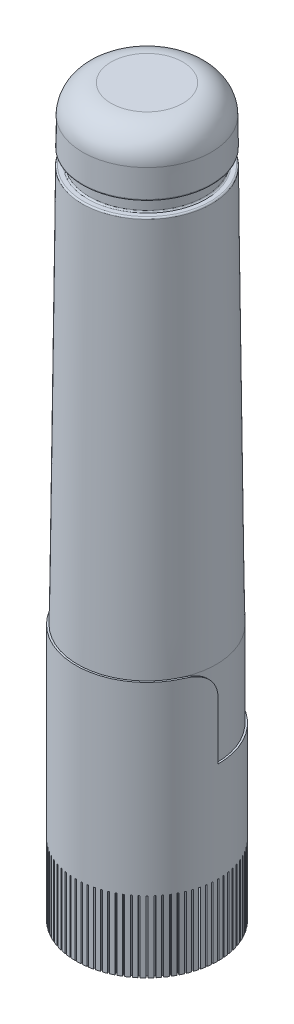
SolidWorks part; units mm, degrees
ref_plane "Front Plane" through (0, 0, 0) normal (0, 0, 1) x (1, 0, 0)
ref_plane "Top Plane" through (0, 0, 0) normal (0, 1, 0) x (1, 0, 0)
ref_plane "Right Plane" through (0, 0, 0) normal (1, 0, 0) x (0, 0, -1)
sketch "Sketch1" plane through (0, 0, 0) normal (0, 1, 0) x (1, 0, 0)
  circle A0 centre (0, 0) radius 5
  dimension "D1" = 10
extrude "Boss-Extrude1" add sketch "Sketch1" along normal blind 18
sketch "Sketch2" plane through (0, 0, 0) normal (0, -1, 0) x (-1, 0, 0)
  line L0 (-0.3559, -5.16) -> (-0.4556, -5.1521)
  line L1 (0.05, -5.172) -> (-0.05, -5.172)
  line L2 (0.05, -5.172) -> (0.05, -4.828)
  line L3 (0.05, -4.828) -> (-0.05, -4.828)
  line L4 (-0.05, -5.172) -> (-0.05, -4.828)
  line L5 (0.05, -5.172) -> (-0.05, -4.828) construction
  line L6 (0.05, -4.828) -> (-0.05, -5.172) construction
  line L7 (-0.3559, -5.16) -> (-0.329, -4.817)
  line L8 (-0.4556, -5.1521) -> (-0.4286, -4.8092)
  line L9 (-0.329, -4.817) -> (-0.4286, -4.8092)
  line L10 (-0.7597, -5.1162) -> (-0.8585, -5.1005)
  line L11 (-0.7597, -5.1162) -> (-0.7059, -4.7764)
  line L12 (-0.8585, -5.1005) -> (-0.8046, -4.7607)
  line L13 (-0.7059, -4.7764) -> (-0.8046, -4.7607)
  line L14 (-1.1588, -5.0408) -> (-1.256, -5.0174)
  line L15 (-1.1588, -5.0408) -> (-1.0785, -4.7063)
  line L16 (-1.256, -5.0174) -> (-1.1757, -4.6829)
  line L17 (-1.0785, -4.7063) -> (-1.1757, -4.6829)
  line L18 (-1.5507, -4.9343) -> (-1.6458, -4.9034)
  line L19 (-1.5507, -4.9343) -> (-1.4444, -4.6071)
  line L20 (-1.6458, -4.9034) -> (-1.5395, -4.5762)
  line L21 (-1.4444, -4.6071) -> (-1.5395, -4.5762)
  line L22 (-1.933, -4.7974) -> (-2.0254, -4.7592)
  line L23 (-1.933, -4.7974) -> (-1.8014, -4.4796)
  line L24 (-2.0254, -4.7592) -> (-1.8938, -4.4413)
  line L25 (-1.8014, -4.4796) -> (-1.8938, -4.4413)
  line L26 (-2.3035, -4.631) -> (-2.3926, -4.5856)
  line L27 (-2.3035, -4.631) -> (-2.1473, -4.3245)
  line L28 (-2.3926, -4.5856) -> (-2.2364, -4.2791)
  line L29 (-2.1473, -4.3245) -> (-2.2364, -4.2791)
  line L30 (-2.6597, -4.436) -> (-2.745, -4.3837)
  line L31 (-2.6597, -4.436) -> (-2.48, -4.1427)
  line L32 (-2.745, -4.3837) -> (-2.5652, -4.0904)
  line L33 (-2.48, -4.1427) -> (-2.5652, -4.0904)
  line L34 (-2.9996, -4.2136) -> (-3.0805, -4.1549)
  line L35 (-2.9996, -4.2136) -> (-2.7974, -3.9353)
  line L36 (-3.0805, -4.1549) -> (-2.8783, -3.8765)
  line L37 (-2.7974, -3.9353) -> (-2.8783, -3.8765)
  line L38 (-3.3209, -3.9653) -> (-3.397, -3.9004)
  line L39 (-3.3209, -3.9653) -> (-3.0975, -3.7037)
  line L40 (-3.397, -3.9004) -> (-3.1735, -3.6388)
  line L41 (-3.0975, -3.7037) -> (-3.1735, -3.6388)
  line L42 (-3.6218, -3.6925) -> (-3.6925, -3.6218)
  line L43 (-3.6218, -3.6925) -> (-3.3785, -3.4493)
  line L44 (-3.6925, -3.6218) -> (-3.4493, -3.3785)
  line L45 (-3.3785, -3.4493) -> (-3.4493, -3.3785)
  line L46 (-3.9004, -3.397) -> (-3.9653, -3.3209)
  line L47 (-3.9004, -3.397) -> (-3.6388, -3.1735)
  line L48 (-3.9653, -3.3209) -> (-3.7037, -3.0975)
  line L49 (-3.6388, -3.1735) -> (-3.7037, -3.0975)
  line L50 (-4.1549, -3.0805) -> (-4.2136, -2.9996)
  line L51 (-4.1549, -3.0805) -> (-3.8765, -2.8783)
  line L52 (-4.2136, -2.9996) -> (-3.9353, -2.7974)
  line L53 (-3.8765, -2.8783) -> (-3.9353, -2.7974)
  line L54 (-4.3837, -2.745) -> (-4.436, -2.6597)
  line L55 (-4.3837, -2.745) -> (-4.0904, -2.5652)
  line L56 (-4.436, -2.6597) -> (-4.1427, -2.48)
  line L57 (-4.0904, -2.5652) -> (-4.1427, -2.48)
  line L58 (-4.5856, -2.3926) -> (-4.631, -2.3035)
  line L59 (-4.5856, -2.3926) -> (-4.2791, -2.2364)
  line L60 (-4.631, -2.3035) -> (-4.3245, -2.1473)
  line L61 (-4.2791, -2.2364) -> (-4.3245, -2.1473)
  line L62 (-4.7592, -2.0254) -> (-4.7974, -1.933)
  line L63 (-4.7592, -2.0254) -> (-4.4413, -1.8938)
  line L64 (-4.7974, -1.933) -> (-4.4796, -1.8014)
  line L65 (-4.4413, -1.8938) -> (-4.4796, -1.8014)
  line L66 (-4.9034, -1.6458) -> (-4.9343, -1.5507)
  line L67 (-4.9034, -1.6458) -> (-4.5762, -1.5395)
  line L68 (-4.9343, -1.5507) -> (-4.6071, -1.4444)
  line L69 (-4.5762, -1.5395) -> (-4.6071, -1.4444)
  line L70 (-5.0174, -1.256) -> (-5.0408, -1.1588)
  line L71 (-5.0174, -1.256) -> (-4.6829, -1.1757)
  line L72 (-5.0408, -1.1588) -> (-4.7063, -1.0785)
  line L73 (-4.6829, -1.1757) -> (-4.7063, -1.0785)
  line L74 (-5.1005, -0.8585) -> (-5.1162, -0.7597)
  line L75 (-5.1005, -0.8585) -> (-4.7607, -0.8046)
  line L76 (-5.1162, -0.7597) -> (-4.7764, -0.7059)
  line L77 (-4.7607, -0.8046) -> (-4.7764, -0.7059)
  line L78 (-5.1521, -0.4556) -> (-5.16, -0.3559)
  line L79 (-5.1521, -0.4556) -> (-4.8092, -0.4286)
  line L80 (-5.16, -0.3559) -> (-4.817, -0.329)
  line L81 (-4.8092, -0.4286) -> (-4.817, -0.329)
  line L82 (-5.172, -0.05) -> (-5.172, 0.05)
  line L83 (-5.172, -0.05) -> (-4.828, -0.05)
  line L84 (-5.172, 0.05) -> (-4.828, 0.05)
  line L85 (-4.828, -0.05) -> (-4.828, 0.05)
  line L86 (-5.16, 0.3559) -> (-5.1521, 0.4556)
  line L87 (-5.16, 0.3559) -> (-4.817, 0.329)
  line L88 (-5.1521, 0.4556) -> (-4.8092, 0.4286)
  line L89 (-4.817, 0.329) -> (-4.8092, 0.4286)
  line L90 (-5.1162, 0.7597) -> (-5.1005, 0.8585)
  line L91 (-5.1162, 0.7597) -> (-4.7764, 0.7059)
  line L92 (-5.1005, 0.8585) -> (-4.7607, 0.8046)
  line L93 (-4.7764, 0.7059) -> (-4.7607, 0.8046)
  line L94 (-5.0408, 1.1588) -> (-5.0174, 1.256)
  line L95 (-5.0408, 1.1588) -> (-4.7063, 1.0785)
  line L96 (-5.0174, 1.256) -> (-4.6829, 1.1757)
  line L97 (-4.7063, 1.0785) -> (-4.6829, 1.1757)
  line L98 (-4.9343, 1.5507) -> (-4.9034, 1.6458)
  line L99 (-4.9343, 1.5507) -> (-4.6071, 1.4444)
  line L100 (-4.9034, 1.6458) -> (-4.5762, 1.5395)
  line L101 (-4.6071, 1.4444) -> (-4.5762, 1.5395)
  line L102 (-4.7974, 1.933) -> (-4.7592, 2.0254)
  line L103 (-4.7974, 1.933) -> (-4.4796, 1.8014)
  line L104 (-4.7592, 2.0254) -> (-4.4413, 1.8938)
  line L105 (-4.4796, 1.8014) -> (-4.4413, 1.8938)
  line L106 (-4.631, 2.3035) -> (-4.5856, 2.3926)
  line L107 (-4.631, 2.3035) -> (-4.3245, 2.1473)
  line L108 (-4.5856, 2.3926) -> (-4.2791, 2.2364)
  line L109 (-4.3245, 2.1473) -> (-4.2791, 2.2364)
  line L110 (-4.436, 2.6597) -> (-4.3837, 2.745)
  line L111 (-4.436, 2.6597) -> (-4.1427, 2.48)
  line L112 (-4.3837, 2.745) -> (-4.0904, 2.5652)
  line L113 (-4.1427, 2.48) -> (-4.0904, 2.5652)
  line L114 (-4.2136, 2.9996) -> (-4.1549, 3.0805)
  line L115 (-4.2136, 2.9996) -> (-3.9353, 2.7974)
  line L116 (-4.1549, 3.0805) -> (-3.8765, 2.8783)
  line L117 (-3.9353, 2.7974) -> (-3.8765, 2.8783)
  line L118 (-3.9653, 3.3209) -> (-3.9004, 3.397)
  line L119 (-3.9653, 3.3209) -> (-3.7037, 3.0975)
  line L120 (-3.9004, 3.397) -> (-3.6388, 3.1735)
  line L121 (-3.7037, 3.0975) -> (-3.6388, 3.1735)
  line L122 (-3.6925, 3.6218) -> (-3.6218, 3.6925)
  line L123 (-3.6925, 3.6218) -> (-3.4493, 3.3785)
  line L124 (-3.6218, 3.6925) -> (-3.3785, 3.4493)
  line L125 (-3.4493, 3.3785) -> (-3.3785, 3.4493)
  line L126 (-3.397, 3.9004) -> (-3.3209, 3.9653)
  line L127 (-3.397, 3.9004) -> (-3.1735, 3.6388)
  line L128 (-3.3209, 3.9653) -> (-3.0975, 3.7037)
  line L129 (-3.1735, 3.6388) -> (-3.0975, 3.7037)
  line L130 (-3.0805, 4.1549) -> (-2.9996, 4.2136)
  line L131 (-3.0805, 4.1549) -> (-2.8783, 3.8765)
  line L132 (-2.9996, 4.2136) -> (-2.7974, 3.9353)
  line L133 (-2.8783, 3.8765) -> (-2.7974, 3.9353)
  line L134 (-2.745, 4.3837) -> (-2.6597, 4.436)
  line L135 (-2.745, 4.3837) -> (-2.5652, 4.0904)
  line L136 (-2.6597, 4.436) -> (-2.48, 4.1427)
  line L137 (-2.5652, 4.0904) -> (-2.48, 4.1427)
  line L138 (-2.3926, 4.5856) -> (-2.3035, 4.631)
  line L139 (-2.3926, 4.5856) -> (-2.2364, 4.2791)
  line L140 (-2.3035, 4.631) -> (-2.1473, 4.3245)
  line L141 (-2.2364, 4.2791) -> (-2.1473, 4.3245)
  line L142 (-2.0254, 4.7592) -> (-1.933, 4.7974)
  line L143 (-2.0254, 4.7592) -> (-1.8938, 4.4413)
  line L144 (-1.933, 4.7974) -> (-1.8014, 4.4796)
  line L145 (-1.8938, 4.4413) -> (-1.8014, 4.4796)
  line L146 (-1.6458, 4.9034) -> (-1.5507, 4.9343)
  line L147 (-1.6458, 4.9034) -> (-1.5395, 4.5762)
  line L148 (-1.5507, 4.9343) -> (-1.4444, 4.6071)
  line L149 (-1.5395, 4.5762) -> (-1.4444, 4.6071)
  line L150 (-1.256, 5.0174) -> (-1.1588, 5.0408)
  line L151 (-1.256, 5.0174) -> (-1.1757, 4.6829)
  line L152 (-1.1588, 5.0408) -> (-1.0785, 4.7063)
  line L153 (-1.1757, 4.6829) -> (-1.0785, 4.7063)
  line L154 (-0.8585, 5.1005) -> (-0.7597, 5.1162)
  line L155 (-0.8585, 5.1005) -> (-0.8046, 4.7607)
  line L156 (-0.7597, 5.1162) -> (-0.7059, 4.7764)
  line L157 (-0.8046, 4.7607) -> (-0.7059, 4.7764)
  line L158 (-0.4556, 5.1521) -> (-0.3559, 5.16)
  line L159 (-0.4556, 5.1521) -> (-0.4286, 4.8092)
  line L160 (-0.3559, 5.16) -> (-0.329, 4.817)
  line L161 (-0.4286, 4.8092) -> (-0.329, 4.817)
  line L162 (-0.05, 5.172) -> (0.05, 5.172)
  line L163 (-0.05, 5.172) -> (-0.05, 4.828)
  line L164 (0.05, 5.172) -> (0.05, 4.828)
  line L165 (-0.05, 4.828) -> (0.05, 4.828)
  line L166 (0.3559, 5.16) -> (0.4556, 5.1521)
  line L167 (0.3559, 5.16) -> (0.329, 4.817)
  line L168 (0.4556, 5.1521) -> (0.4286, 4.8092)
  line L169 (0.329, 4.817) -> (0.4286, 4.8092)
  line L170 (0.7597, 5.1162) -> (0.8585, 5.1005)
  line L171 (0.7597, 5.1162) -> (0.7059, 4.7764)
  line L172 (0.8585, 5.1005) -> (0.8046, 4.7607)
  line L173 (0.7059, 4.7764) -> (0.8046, 4.7607)
  line L174 (1.1588, 5.0408) -> (1.256, 5.0174)
  line L175 (1.1588, 5.0408) -> (1.0785, 4.7063)
  line L176 (1.256, 5.0174) -> (1.1757, 4.6829)
  line L177 (1.0785, 4.7063) -> (1.1757, 4.6829)
  line L178 (1.5507, 4.9343) -> (1.6458, 4.9034)
  line L179 (1.5507, 4.9343) -> (1.4444, 4.6071)
  line L180 (1.6458, 4.9034) -> (1.5395, 4.5762)
  line L181 (1.4444, 4.6071) -> (1.5395, 4.5762)
  line L182 (1.933, 4.7974) -> (2.0254, 4.7592)
  line L183 (1.933, 4.7974) -> (1.8014, 4.4796)
  line L184 (2.0254, 4.7592) -> (1.8938, 4.4413)
  line L185 (1.8014, 4.4796) -> (1.8938, 4.4413)
  line L186 (2.3035, 4.631) -> (2.3926, 4.5856)
  line L187 (2.3035, 4.631) -> (2.1473, 4.3245)
  line L188 (2.3926, 4.5856) -> (2.2364, 4.2791)
  line L189 (2.1473, 4.3245) -> (2.2364, 4.2791)
  line L190 (2.6597, 4.436) -> (2.745, 4.3837)
  line L191 (2.6597, 4.436) -> (2.48, 4.1427)
  line L192 (2.745, 4.3837) -> (2.5652, 4.0904)
  line L193 (2.48, 4.1427) -> (2.5652, 4.0904)
  line L194 (2.9996, 4.2136) -> (3.0805, 4.1549)
  line L195 (2.9996, 4.2136) -> (2.7974, 3.9353)
  line L196 (3.0805, 4.1549) -> (2.8783, 3.8765)
  line L197 (2.7974, 3.9353) -> (2.8783, 3.8765)
  line L198 (3.3209, 3.9653) -> (3.397, 3.9004)
  line L199 (3.3209, 3.9653) -> (3.0975, 3.7037)
  line L200 (3.397, 3.9004) -> (3.1735, 3.6388)
  line L201 (3.0975, 3.7037) -> (3.1735, 3.6388)
  line L202 (3.6218, 3.6925) -> (3.6925, 3.6218)
  line L203 (3.6218, 3.6925) -> (3.3785, 3.4493)
  line L204 (3.6925, 3.6218) -> (3.4493, 3.3785)
  line L205 (3.3785, 3.4493) -> (3.4493, 3.3785)
  line L206 (3.9004, 3.397) -> (3.9653, 3.3209)
  line L207 (3.9004, 3.397) -> (3.6388, 3.1735)
  line L208 (3.9653, 3.3209) -> (3.7037, 3.0975)
  line L209 (3.6388, 3.1735) -> (3.7037, 3.0975)
  line L210 (4.1549, 3.0805) -> (4.2136, 2.9996)
  line L211 (4.1549, 3.0805) -> (3.8765, 2.8783)
  line L212 (4.2136, 2.9996) -> (3.9353, 2.7974)
  line L213 (3.8765, 2.8783) -> (3.9353, 2.7974)
  line L214 (4.3837, 2.745) -> (4.436, 2.6597)
  line L215 (4.3837, 2.745) -> (4.0904, 2.5652)
  line L216 (4.436, 2.6597) -> (4.1427, 2.48)
  line L217 (4.0904, 2.5652) -> (4.1427, 2.48)
  line L218 (4.5856, 2.3926) -> (4.631, 2.3035)
  line L219 (4.5856, 2.3926) -> (4.2791, 2.2364)
  line L220 (4.631, 2.3035) -> (4.3245, 2.1473)
  line L221 (4.2791, 2.2364) -> (4.3245, 2.1473)
  line L222 (4.7592, 2.0254) -> (4.7974, 1.933)
  line L223 (4.7592, 2.0254) -> (4.4413, 1.8938)
  line L224 (4.7974, 1.933) -> (4.4796, 1.8014)
  line L225 (4.4413, 1.8938) -> (4.4796, 1.8014)
  line L226 (4.9034, 1.6458) -> (4.9343, 1.5507)
  line L227 (4.9034, 1.6458) -> (4.5762, 1.5395)
  line L228 (4.9343, 1.5507) -> (4.6071, 1.4444)
  line L229 (4.5762, 1.5395) -> (4.6071, 1.4444)
  line L230 (5.0174, 1.256) -> (5.0408, 1.1588)
  line L231 (5.0174, 1.256) -> (4.6829, 1.1757)
  line L232 (5.0408, 1.1588) -> (4.7063, 1.0785)
  line L233 (4.6829, 1.1757) -> (4.7063, 1.0785)
  line L234 (5.1005, 0.8585) -> (5.1162, 0.7597)
  line L235 (5.1005, 0.8585) -> (4.7607, 0.8046)
  line L236 (5.1162, 0.7597) -> (4.7764, 0.7059)
  line L237 (4.7607, 0.8046) -> (4.7764, 0.7059)
  line L238 (5.1521, 0.4556) -> (5.16, 0.3559)
  line L239 (5.1521, 0.4556) -> (4.8092, 0.4286)
  line L240 (5.16, 0.3559) -> (4.817, 0.329)
  line L241 (4.8092, 0.4286) -> (4.817, 0.329)
  line L242 (5.172, 0.05) -> (5.172, -0.05)
  line L243 (5.172, 0.05) -> (4.828, 0.05)
  line L244 (5.172, -0.05) -> (4.828, -0.05)
  line L245 (4.828, 0.05) -> (4.828, -0.05)
  line L246 (5.16, -0.3559) -> (5.1521, -0.4556)
  line L247 (5.16, -0.3559) -> (4.817, -0.329)
  line L248 (5.1521, -0.4556) -> (4.8092, -0.4286)
  line L249 (4.817, -0.329) -> (4.8092, -0.4286)
  line L250 (5.1162, -0.7597) -> (5.1005, -0.8585)
  line L251 (5.1162, -0.7597) -> (4.7764, -0.7059)
  line L252 (5.1005, -0.8585) -> (4.7607, -0.8046)
  line L253 (4.7764, -0.7059) -> (4.7607, -0.8046)
  line L254 (5.0408, -1.1588) -> (5.0174, -1.256)
  line L255 (5.0408, -1.1588) -> (4.7063, -1.0785)
  line L256 (5.0174, -1.256) -> (4.6829, -1.1757)
  line L257 (4.7063, -1.0785) -> (4.6829, -1.1757)
  line L258 (4.9343, -1.5507) -> (4.9034, -1.6458)
  line L259 (4.9343, -1.5507) -> (4.6071, -1.4444)
  line L260 (4.9034, -1.6458) -> (4.5762, -1.5395)
  line L261 (4.6071, -1.4444) -> (4.5762, -1.5395)
  line L262 (4.7974, -1.933) -> (4.7592, -2.0254)
  line L263 (4.7974, -1.933) -> (4.4796, -1.8014)
  line L264 (4.7592, -2.0254) -> (4.4413, -1.8938)
  line L265 (4.4796, -1.8014) -> (4.4413, -1.8938)
  line L266 (4.631, -2.3035) -> (4.5856, -2.3926)
  line L267 (4.631, -2.3035) -> (4.3245, -2.1473)
  line L268 (4.5856, -2.3926) -> (4.2791, -2.2364)
  line L269 (4.3245, -2.1473) -> (4.2791, -2.2364)
  line L270 (4.436, -2.6597) -> (4.3837, -2.745)
  line L271 (4.436, -2.6597) -> (4.1427, -2.48)
  line L272 (4.3837, -2.745) -> (4.0904, -2.5652)
  line L273 (4.1427, -2.48) -> (4.0904, -2.5652)
  line L274 (4.2136, -2.9996) -> (4.1549, -3.0805)
  line L275 (4.2136, -2.9996) -> (3.9353, -2.7974)
  line L276 (4.1549, -3.0805) -> (3.8765, -2.8783)
  line L277 (3.9353, -2.7974) -> (3.8765, -2.8783)
  line L278 (3.9653, -3.3209) -> (3.9004, -3.397)
  line L279 (3.9653, -3.3209) -> (3.7037, -3.0975)
  line L280 (3.9004, -3.397) -> (3.6388, -3.1735)
  line L281 (3.7037, -3.0975) -> (3.6388, -3.1735)
  line L282 (3.6925, -3.6218) -> (3.6218, -3.6925)
  line L283 (3.6925, -3.6218) -> (3.4493, -3.3785)
  line L284 (3.6218, -3.6925) -> (3.3785, -3.4493)
  line L285 (3.4493, -3.3785) -> (3.3785, -3.4493)
  line L286 (3.397, -3.9004) -> (3.3209, -3.9653)
  line L287 (3.397, -3.9004) -> (3.1735, -3.6388)
  line L288 (3.3209, -3.9653) -> (3.0975, -3.7037)
  line L289 (3.1735, -3.6388) -> (3.0975, -3.7037)
  line L290 (3.0805, -4.1549) -> (2.9996, -4.2136)
  line L291 (3.0805, -4.1549) -> (2.8783, -3.8765)
  line L292 (2.9996, -4.2136) -> (2.7974, -3.9353)
  line L293 (2.8783, -3.8765) -> (2.7974, -3.9353)
  line L294 (2.745, -4.3837) -> (2.6597, -4.436)
  line L295 (2.745, -4.3837) -> (2.5652, -4.0904)
  line L296 (2.6597, -4.436) -> (2.48, -4.1427)
  line L297 (2.5652, -4.0904) -> (2.48, -4.1427)
  line L298 (2.3926, -4.5856) -> (2.3035, -4.631)
  line L299 (2.3926, -4.5856) -> (2.2364, -4.2791)
  line L300 (2.3035, -4.631) -> (2.1473, -4.3245)
  line L301 (2.2364, -4.2791) -> (2.1473, -4.3245)
  line L302 (2.0254, -4.7592) -> (1.933, -4.7974)
  line L303 (2.0254, -4.7592) -> (1.8938, -4.4413)
  line L304 (1.933, -4.7974) -> (1.8014, -4.4796)
  line L305 (1.8938, -4.4413) -> (1.8014, -4.4796)
  line L306 (1.6458, -4.9034) -> (1.5507, -4.9343)
  line L307 (1.6458, -4.9034) -> (1.5395, -4.5762)
  line L308 (1.5507, -4.9343) -> (1.4444, -4.6071)
  line L309 (1.5395, -4.5762) -> (1.4444, -4.6071)
  line L310 (1.256, -5.0174) -> (1.1588, -5.0408)
  line L311 (1.256, -5.0174) -> (1.1757, -4.6829)
  line L312 (1.1588, -5.0408) -> (1.0785, -4.7063)
  line L313 (1.1757, -4.6829) -> (1.0785, -4.7063)
  line L314 (0.8585, -5.1005) -> (0.7597, -5.1162)
  line L315 (0.8585, -5.1005) -> (0.8046, -4.7607)
  line L316 (0.7597, -5.1162) -> (0.7059, -4.7764)
  line L317 (0.8046, -4.7607) -> (0.7059, -4.7764)
  line L318 (0.4556, -5.1521) -> (0.3559, -5.16)
  line L319 (0.4556, -5.1521) -> (0.4286, -4.8092)
  line L320 (0.3559, -5.16) -> (0.329, -4.817)
  line L321 (0.4286, -4.8092) -> (0.329, -4.817)
  circle A0 centre (0, 0) radius 5 construction
  point P0 (0, -5)
  point P325 (0, 0)
  dimension "D1" = 0.1
  dimension "D2" = 80
extrude "Cut-Extrude1" cut sketch "Sketch2" against normal blind 5
sketch "Sketch3" plane through (0, 18, 0) normal (0, 1, 0) x (1, 0, 0)
  line L1 (5, 0) -> (-5, 0)
  line L2 (5, 0) -> (5, 5)
  line L3 (5, 5) -> (-5, 5)
  line L4 (-5, 0) -> (-5, 5)
  circle A0 centre (0, 0) radius 5 construction
extrude "Cut-Extrude2" cut sketch "Sketch3" against normal blind 6
fillet "Fillet2" radius 2 1 edges at (0, 18, 0)
sketch "Sketch4" plane through (0, 12, 0) normal (0, 1, 0) x (1, 0, 0)
  line L0 (5, 0) -> (-4.875, 0)
  circle A0 centre (0, 0) radius 4.875
  dimension "D1" = 9.75
extrude "Boss-Extrude2" add sketch "Sketch4" along normal blind 6
sketch "Sketch7" plane through (0, 0, 0) normal (1, 0, 0) x (0, 0, -1)
  line L0 (0, 18) -> (0, 51)
  line L1 (0, 51) -> (4.5, 51)
  line L2 (0, 18) -> (4.875, 18)
  line L3 (4.875, 18) -> (4.5, 51)
  dimension "D1" = 33
  dimension "D2" = 4.5
revolve "Revolve1" add sketch "Sketch7" angle 360 about L0
fillet "Fillet6" radius 2 1 edges at (0, 51, -4.5)
sketch "Sketch8" plane through (0, 0, 0) normal (1, 0, 0) x (0, 0, -1)
  line L0 (0, 51) -> (0.05, 0) construction
  line L1 (2.5226, 51) -> (-2.5226, 51) construction
  line L3 (4.0726, 47) -> (4.8226, 47)
  line L4 (4.0726, 47) -> (4.0726, 46)
  line L5 (4.0726, 46) -> (4.8226, 46)
  line L6 (4.8226, 47) -> (4.8226, 46)
  point P9 (4.0726, 46.5)
  point P10 (4.8226, 46.5)
  dimension "D1" = 5
  dimension "D2" = 0.75
  dimension "D3" = 2.3
  dimension "D4" = 1
revolve "Cut-Revolve3" cut sketch "Sketch8" angle 360 about L0
fillet "Fillet7" radius 0.1 4 edges at (0, 46.992, 4.0647) (0, 45.992, 4.0628) (2.9967, 45.9922, 3.4329) (4.2063, 46.9938, 1.723)
